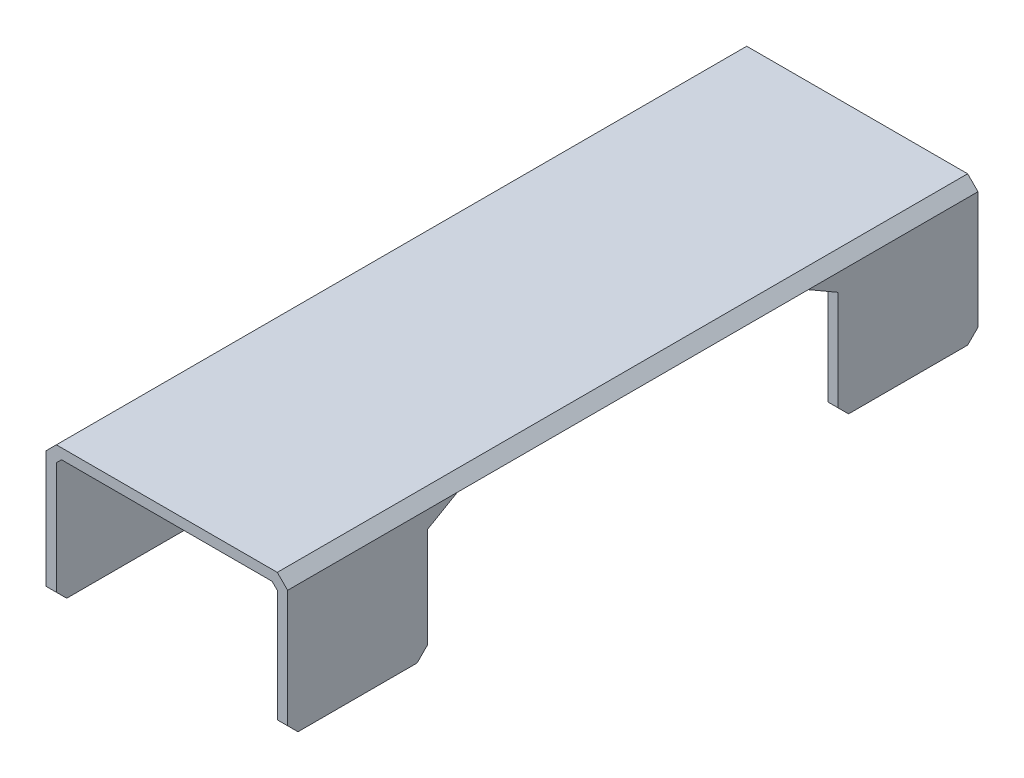
SolidWorks part; units mm, degrees
ref_plane "Front Plane" through (0, 0, 0) normal (0, 0, 1) x (1, 0, 0)
ref_plane "Top Plane" through (0, 0, 0) normal (0, 1, 0) x (1, 0, 0)
ref_plane "Right Plane" through (0, 0, 0) normal (1, 0, 0) x (0, 0, -1)
sketch "Sketch2" plane through (0, 0, 0) normal (0, 1, 0) x (1, 0, 0)
  line L1 (-32, -100) -> (32, -100)
  line L2 (-32, -100) -> (-32, 100)
  line L3 (-32, 100) -> (32, 100)
  line L4 (32, -100) -> (32, 100)
  line L5 (-32, -100) -> (32, 100) construction
  line L6 (-32, 100) -> (32, -100) construction
  point P0 (0, 0)
  dimension "D1" = 64
  dimension "D2" = 200
extrude "Boss-Extrude1" add sketch "Sketch2" along normal blind 3
sketch "Sketch13" plane through (0, 0, 100) normal (0, 0, 1) x (1, 0, 0)
  line L1 (32, 3) -> (35, 3)
  line L2 (32, 3) -> (32, -37)
  line L3 (32, -37) -> (35, -37)
  line L4 (35, 3) -> (35, -37)
  line L5 (-32, 3) -> (-35, 3)
  line L6 (-32, 3) -> (-32, -37)
  line L7 (-32, -37) -> (-35, -37)
  line L8 (-35, 3) -> (-35, -37)
  point P10 (38.2609, 43.6773)
  point P11 (35, -19.8465)
  point P12 (0, 0)
  point P13 (-32, 3)
  point P15 (32, 3)
  dimension "D1" = 3
  dimension "D2" = 40
extrude "Boss-Extrude2" add sketch "Sketch13" against normal up to surface (200 mm away) up to face at (0, 1.5, -100)
chamfer "Chamfer1" distance 1.5 angle 45 2 edges at (-32, 0, 0) (32, 0, 0)
chamfer "Chamfer2" distance 3 angle 45 2 edges at (35, 3, 0) (-35, 3, 0)
sketch "Sketch14" plane through (35, 0, 0) normal (1, 0, 0) x (0, 0, -1)
  line L0 (100, 0) -> (-100, 0) construction
  line L1 (-59.5, 0) -> (59.5, 0)
  line L2 (-59.5, 0) -> (-59.5, -37)
  line L3 (-59.5, -37) -> (59.5, -37)
  line L4 (59.5, 0) -> (59.5, -37)
  line L5 (100, -37) -> (-100, -37) construction
  point P8 (0, 0)
  dimension "D1" = 119
extrude "Cut-Extrude1" cut sketch "Sketch14" against normal up to surface (70 mm away) up to face at (-35, -18.5, 0)
chamfer "Chamfer3" distance 5 angle 60 4 edges at (32.75, 0, -59.5) (-32.75, 0, -59.5) (32.75, 0, 59.5) (-32.75, 0, 59.5) first distance on face at (32.9, -15.1, -59.5) first distance on face at (-32.9, -15.1, -59.5) first distance on face at (32.9, -15.1, 59.5) first distance on face at (-32.9, -15.1, 59.5)
chamfer "Chamfer4" distance 3 angle 45 8 edges at (33.5, -37, -100) (-33.5, -37, -100) (-33.5, -37, 100) (33.5, -37, 100) (33.5, -37, 59.5) (-33.5, -37, 59.5) (-33.5, -37, -59.5) (33.5, -37, -59.5)
